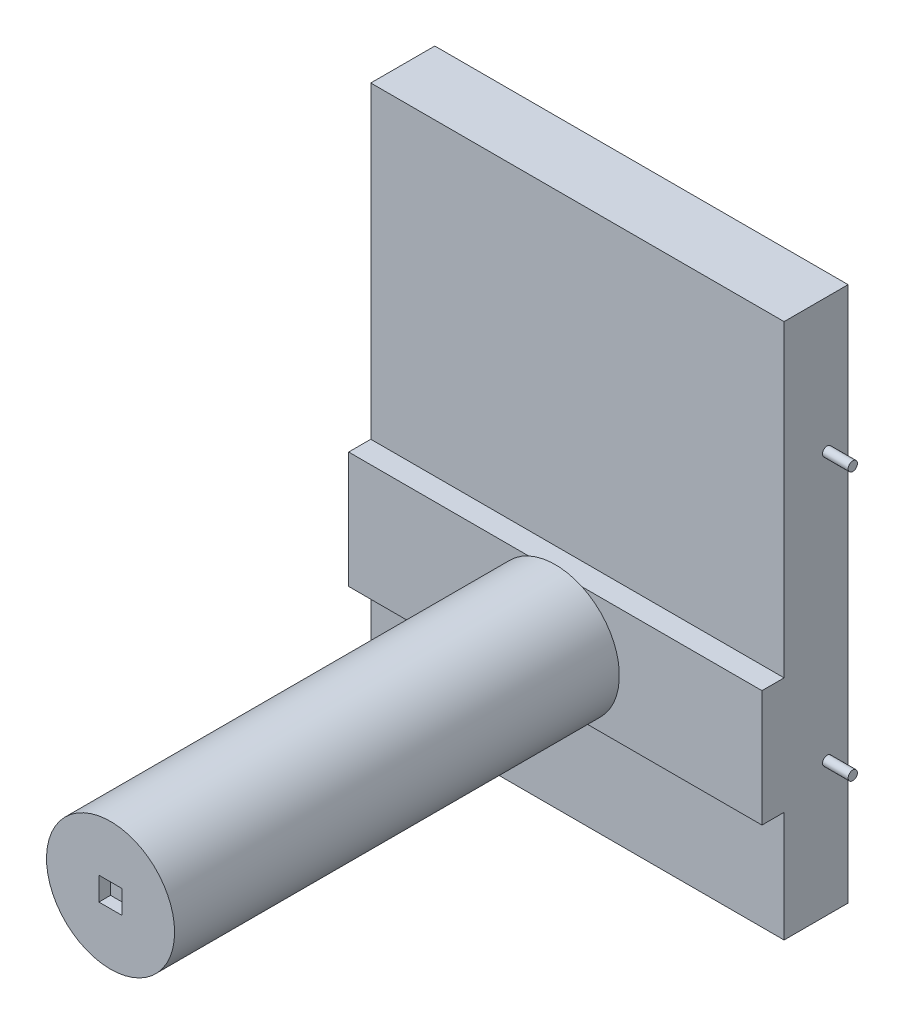
SolidWorks part; units mm, degrees
ref_plane "Front Plane" through (0, 0, 0) normal (0, 0, 1) x (1, 0, 0)
ref_plane "Top Plane" through (0, 0, 0) normal (0, 1, 0) x (1, 0, 0)
ref_plane "Right Plane" through (0, 0, 0) normal (1, 0, 0) x (0, 0, -1)
other "Center of Mass"
ref_plane "Plane1" through (355, 0, 0) normal (1, 0, 0) x (0, 0, -1)
sketch "Sketch1" plane through (355, 0, 0) normal (1, 0, 0) x (0, 0, -1)
  line L0 (-32, 460) -> (-87, 460)
  line L1 (-87, 460) -> (-87, 195)
  line L2 (-87, 195) -> (-106, 195)
  line L3 (-106, 195) -> (-106, 95)
  line L4 (-106, 95) -> (-87, 95)
  line L5 (-87, 95) -> (-87, 0)
  line L6 (-87, 0) -> (-32, 0)
  line L7 (-32, 0) -> (-32, 460)
extrude "Boss-Extrude1" add sketch "Sketch1" against normal blind 355
sketch "Sketch2" plane through (355, 0, 0) normal (1, 0, 0) x (0, 0, -1)
  line L0 (-87, 0) -> (-32, 0) construction
  line L1 (-32, 460) -> (-50, 460)
  line L2 (-32, 460) -> (-32, 0)
  line L3 (-32, 0) -> (-50, 0)
  line L6 (-32, 460) -> (-50, 460)
  line L7 (-32, 460) -> (-32, 345)
  line L10 (-32, 0) -> (-50, 0)
  line L11 (-32, 0) -> (-32, 115)
  circle A0 centre (-50, 345) radius 4
  circle A1 centre (-50, 115) radius 4
  dimension "D1" = 18
extrude "Boss-Extrude2" add sketch "Sketch2" along normal blind 22 contours A0 region at (355, 345, 50)
sketch "Sketch3" plane through (355, 0, 0) normal (1, 0, 0) x (0, 0, -1)
  circle A0 centre (-50, 115) radius 4
extrude "Boss-Extrude3" add sketch "Sketch3" along normal blind 22
sketch "Sketch4" plane through (0, 0, 0) normal (-1, 0, 0) x (0, 0, 1)
  circle A0 centre (50, 115) radius 4
extrude "Boss-Extrude4" add sketch "Sketch4" along normal blind 22
sketch "Sketch5" plane through (0, 0, 0) normal (-1, 0, 0) x (0, 0, 1)
  circle A0 centre (50, 345) radius 4
extrude "Boss-Extrude5" add sketch "Sketch5" along normal blind 22
sketch "Sketch6" plane through (0, 0, 106) normal (0, 0, 1) x (1, 0, 0)
  circle A0 centre (177.5, 145) radius 55
extrude "Boss-Extrude6" add sketch "Sketch6" along normal blind 382 contours A0
sketch "Sketch8" plane through (0, 0, 488) normal (0, 0, 1) x (1, 0, 0)
  line L0 (177.5, 200) -> (177.5, 90) construction
  line L1 (122.5, 145) -> (232.5, 145) construction
  line L3 (187.5, 170) -> (167.5, 170)
  line L4 (187.5, 170) -> (187.5, 120)
  line L5 (187.5, 120) -> (167.5, 120)
  line L6 (167.5, 170) -> (167.5, 120)
  line L7 (187.5, 170) -> (167.5, 120) construction
  line L8 (187.5, 120) -> (167.5, 170) construction
  circle A0 centre (177.5, 145) radius 55 construction
  arc A1 (154.5871, 195) -> (154.5871, 95) centre (177.5, 145) ccw construction
  arc A2 (200.4129, 95) -> (200.4129, 195) centre (177.5, 145) ccw construction
  point P13 (177.5, 145)
extrude "Cut-Extrude1" cut sketch "Sketch8" against normal blind 10 contours L4 L3 L6 L5
other "Move Face1" face at (177.5, 170, 483) face at (177.5, 120, 483) offset 15 parameters "D1"=15
ref_plane "Plane2" through (0, 0, 0) normal (0, 0, -1) x (-1, 0, 0)
ref_plane "Plane3" through (0, 145, 0) normal (0, -1, 0) x (-1, 0, 0)
ref_plane "Plane4" through (177.5, 0, 0) normal (-1, 0, 0) x (0, 0, 1)
ref_axis "Axis1" through (372.75, 145, 0) along (-1, 0, 0)
ref_axis "Axis2" through (177.5, -23, 0) along (0, 1, 0)
